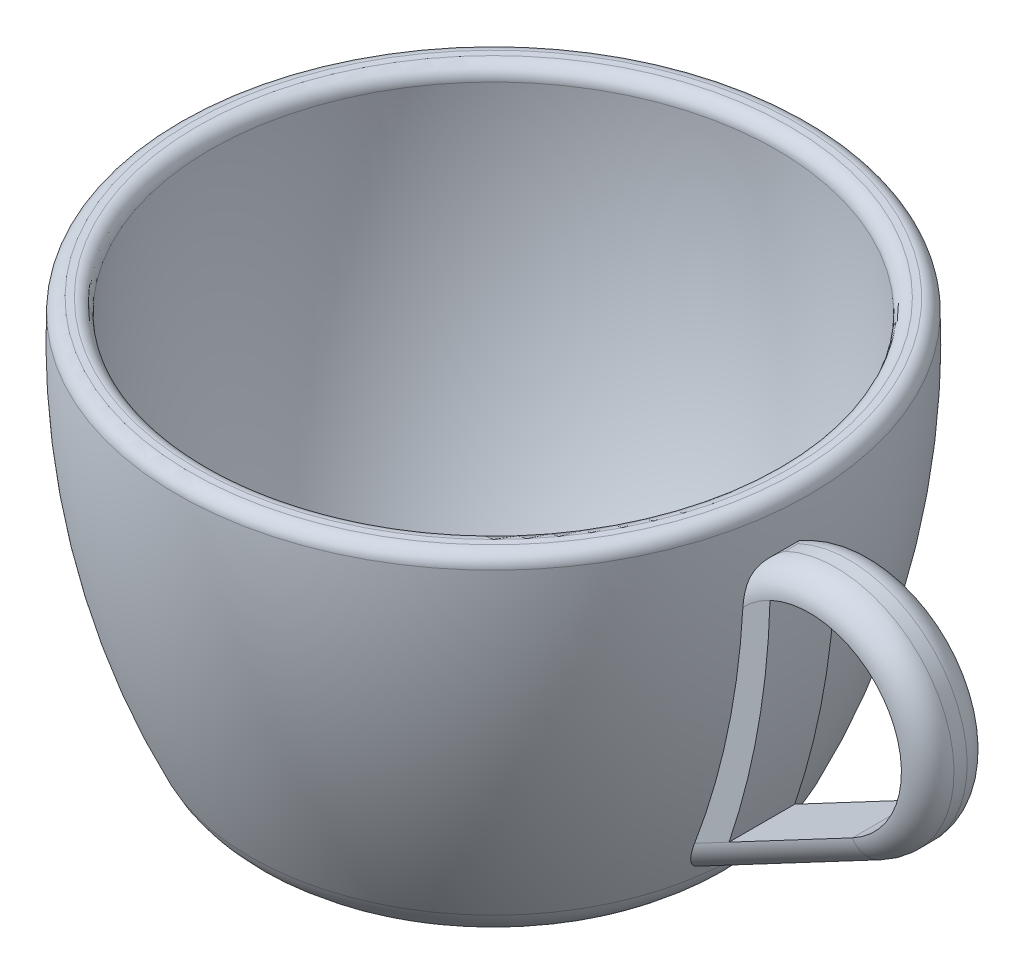
SolidWorks part; units mm, degrees
ref_plane "Alzado" through (0, 0, 0) normal (0, 0, 1) x (1, 0, 0)
ref_plane "Planta" through (0, 0, 0) normal (0, 1, 0) x (1, 0, 0)
ref_plane "Vista lateral" through (0, 0, 0) normal (1, 0, 0) x (0, 0, -1)
sketch "Croquis3" plane through (0, 0, 0) normal (0, 0, 1) x (1, 0, 0)
  line L0 (0, -15.25) -> (0, 15.25)
  line L1 (0, 15.25) -> (24, 15.25)
  line L2 (0, -15.25) -> (17, -15.25)
  arc A0 (24, 15.25) -> (17, -15.25) centre (-33.9344, 12.4932) cw
  point P3 (0, 0)
  dimension "D4" = 58
  dimension "D1" = 30.5
  dimension "D2" = 24
  dimension "D3" = 17
revolve "Revolución1" add sketch "Croquis3" angle 360 about L0
sketch "Croquis6" plane through (0, 15.25, 0) normal (0, 1, 0) x (1, 0, 0)
  circle A0 centre (0, 0) radius 21.5
  dimension "D1" = 43
extrude "Saliente-Extruir1" add sketch "Croquis6" against normal blind 0.1
shell "Vaciado2" thickness 2.5 removed face at (24, 15.25, 0) removed face at (24, 15.25, 0)
fillet "Redondeo2" radius 1 2 edges at (24, 15.25, 0) (-21.497, 15.25, 0)
sketch "Croquis10" plane through (0, -12.75, 0) normal (0, 1, 0) x (1, 0, 0)
fillet "Redondeo3" radius 5 1 edges at (17, -15.25, 0)
sketch "Croquis15" plane through (0, 0, 0) normal (0, 0, 1) x (1, 0, 0)
  line L0 (19.118, -10.9468) -> (33.2542, -3.4522)
  line L1 (22.9248, -6.6649) -> (32.3174, -1.6852)
  arc A0 (24.0635, 11.9993) -> (33.2542, -3.4522) centre (29.0385, 4.4994) cw
  arc A1 (18.454, -12.3956) -> (24.038, 14.2808) centre (-33.9344, 12.4932) ccw construction
  arc A2 (24.038, 14.2808) -> (23.0385, 15.25) centre (23.0385, 14.25) ccw construction
  arc A3 (24.0635, 11.9993) -> (19.118, -10.9468) centre (-33.9344, 12.4932) cw
  arc A4 (26.0424, 10.8258) -> (32.3174, -1.6852) centre (29.0385, 4.4994) cw
  arc A5 (26.0424, 10.8258) -> (22.9248, -6.6649) centre (-33.9344, 12.4932) cw
  dimension "D1" = 9
  dimension "D4" = 2
  dimension "D2" = 6
  dimension "D3" = 16
extrude "Saliente-Extruir2" add sketch "Croquis15" along normal blind 5 separate body
fillet "Redondeo4" radius 2 5 edges at (26.1861, -7.1995, 5) (26.1861, -7.1995, 0) (36.7736, 9.1003, 5) (24.0635, 11.9993, 2.5) (36.7736, 9.1003, 0)
